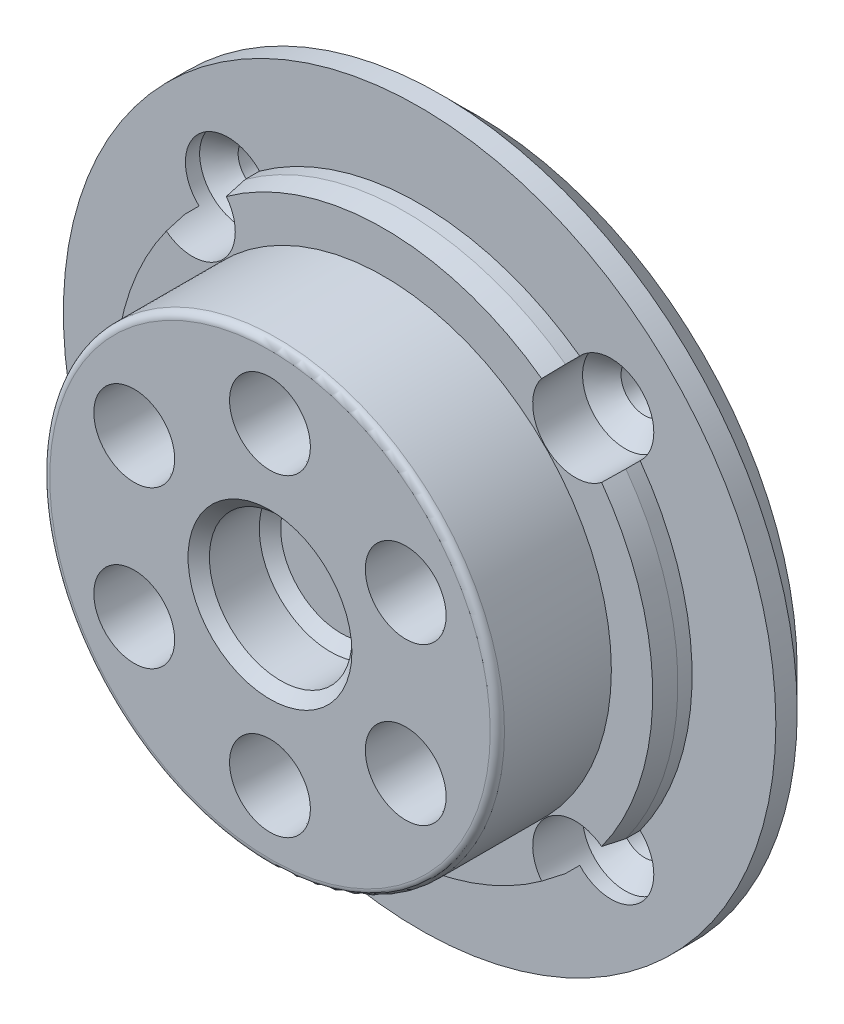
SolidWorks part; units mm, degrees
ref_plane "Front Plane" through (0, 0, 0) normal (0, 0, 1) x (1, 0, 0)
ref_plane "Top Plane" through (0, 0, 0) normal (0, 1, 0) x (1, 0, 0)
ref_plane "Right Plane" through (0, 0, 0) normal (1, 0, 0) x (0, 0, -1)
sketch "Sketch1" plane through (0, 0, 0) normal (0, 0, 1) x (1, 0, 0)
  circle A0 centre (0, 0) radius 25
  dimension "D1" = 50
extrude "Boss-Extrude1" add sketch "Sketch1" along normal blind 4
sketch "Sketch2" plane through (0, 0, 4) normal (0, 0, 1) x (1, 0, 0)
  circle A0 centre (0, 0) radius 19.125
  dimension "D1" = 38.25
extrude "Boss-Extrude2" add sketch "Sketch2" along normal blind 2.5
sketch "Sketch3" plane through (0, 0, 6.5) normal (0, 0, 1) x (1, 0, 0)
  circle A0 centre (0, 0) radius 15.9575
  dimension "D1" = 31.915
extrude "Boss-Extrude3" add sketch "Sketch3" along normal blind 8
sketch "Sketch4" plane through (0, 0, 0) normal (0, 0, -1) x (-1, 0, 0)
  circle A0 centre (0, 16.9333) radius 2.5
  circle A1 centre (16.9333, 0) radius 2.5
  circle A2 centre (0, -16.9333) radius 2.5
  circle A3 centre (-16.9333, 0) radius 2.5
  point P12 (0, 0)
  dimension "D1" = 16.9333
  dimension "D2" = 5
  dimension "D3" = 4
extrude "Cut-Extrude1" cut sketch "Sketch4" against normal blind 3
sketch "Sketch7" plane through (0, 0, 14.5) normal (0, 0, 1) x (1, 0, 0)
  circle A0 centre (0, 11) radius 2.5
  circle A1 centre (9.5263, 5.5) radius 2.5
  circle A2 centre (9.5263, -5.5) radius 2.5
  circle A3 centre (0, -11) radius 2.5
  circle A4 centre (-9.5263, -5.5) radius 2.5
  circle A5 centre (-9.5263, 5.5) radius 2.5
  point P15 (0, 0)
  dimension "D1" = 11
  dimension "D2" = 5
  dimension "D3" = 6
extrude "Cut-Extrude3" cut sketch "Sketch7" against normal blind 11
sketch "Sketch8" plane through (0, 0, 0) normal (0, 0, -1) x (-1, 0, 0)
  circle A0 centre (0, 0) radius 5
  dimension "D1" = 10
extrude "Cut-Extrude4" cut sketch "Sketch8" against normal blind 4
chamfer "Chamfer1" distance 2.5 angle 45 1 edges at (25, 0, 0)
fillet "Fillet1" radius 0.5 1 edges at (15.9575, 0, 14.5)
sketch "Sketch11" plane through (0, 0, 4) normal (0, 0, 1) x (1, 0, 0)
  line L0 (0, 0) -> (-22.4299, 22.4299) construction
  circle A0 centre (-13.435, 13.435) radius 1.65
  circle A1 centre (13.435, 13.435) radius 1.65
  circle A2 centre (13.435, -13.435) radius 1.65
  circle A3 centre (-13.435, -13.435) radius 1.65
  point P14 (0, 0)
  dimension "D1" = 3.3
  dimension "D2" = 19
  dimension "D3" = 4
extrude "Cut-Extrude7" cut sketch "Sketch11" against normal through all both and the other way through all
sketch "Sketch12" plane through (0, 0, 6.5) normal (0, 0, 1) x (1, 0, 0)
  circle A0 centre (-13.435, 13.435) radius 3
  circle A1 centre (13.435, 13.435) radius 3
  circle A2 centre (13.435, -13.435) radius 3
  circle A3 centre (-13.435, -13.435) radius 3
  point P12 (0, 0)
  dimension "D1" = 6
  dimension "D2" = 4
extrude "Cut-Extrude8" cut sketch "Sketch12" against normal blind 5
sketch "Sketch13" plane through (0, 0, 0) normal (0, 0, -1) x (-1, 0, 0)
  circle A0 centre (-10, 0) radius 1.25
  circle A1 centre (-5, 8.6603) radius 1.25
  circle A2 centre (5, 8.6603) radius 1.25
  circle A3 centre (10, 0) radius 1.25
  circle A4 centre (5, -8.6603) radius 1.25
  circle A5 centre (-5, -8.6603) radius 1.25
  point P15 (0, 0)
  dimension "D1" = 2.5
  dimension "D2" = 10
  dimension "D3" = 6
extrude "Cut-Extrude9" [suppressed] cut sketch "Sketch13" against normal blind 12
sketch "Sketch14" [suppressed] plane through (0, 0, 0) normal (0, 0, -1) x (-1, 0, 0)
  circle A0 centre (-10, 0) radius 3
  circle A1 centre (-5, 8.6603) radius 3
  circle A2 centre (5, 8.6603) radius 3
  circle A3 centre (10, 0) radius 3
  circle A4 centre (5, -8.6603) radius 3
  circle A5 centre (-5, -8.6603) radius 3
  point P16 (0, 0)
  dimension "D1" = 6
  dimension "D2" = 6
extrude "Cut-Extrude10" [suppressed] cut sketch "Sketch14" against normal blind 3
sketch "Sketch15" plane through (0, 0, 14.5) normal (0, 0, 1) x (1, 0, 0)
  circle A0 centre (0, 0) radius 5
  dimension "D1" = 10
extrude "Cut-Extrude11" cut sketch "Sketch15" against normal blind 5
chamfer "Chamfer2" distance 1.5 angle 45 4 edges at (16.435, -13.435, 1.5) (-10.435, -13.435, 1.5) (16.435, 13.435, 1.5) (-10.435, 13.435, 1.5)
fillet "Fillet2" radius 2 1 edges at (-5, 0, 4)
chamfer "Chamfer3" distance 1.5 angle 10 4 edges at (0, -19.125, 6.5) (-19.125, 0, 6.5) (19.125, 0, 6.5) (0, 19.125, 6.5) first distance on face at (0, -17.3005, 5.25) first distance on face at (-17.3005, 0, 5.25) first distance on face at (17.3005, 0, 5.25) first distance on face at (0, 17.3005, 5.25)
chamfer "Chamfer4" distance 0.75 angle 45 1 edges at (5, 0, 9.5)
chamfer "Chamfer5" distance 0.75 angle 45 1 edges at (5, 0, 14.5)
sketch "Sketch16" plane through (0, 0, 3.5) normal (0, 0, 1) x (1, 0, 0)
  circle A0 centre (-9.5263, -5.5) radius 0.75
  circle A1 centre (-9.5263, 5.5) radius 0.75
  circle A2 centre (0, 11) radius 0.75
  circle A3 centre (9.5263, 5.5) radius 0.75
  circle A4 centre (9.5263, -5.5) radius 0.75
  circle A5 centre (0, -11) radius 0.75
  point P16 (0, 0)
  dimension "D1" = 1.5
  dimension "D2" = 6
extrude "Cut-Extrude12" cut sketch "Sketch16" against normal through all
chamfer "Chamfer6" distance 0.4 angle 45 4 edges at (-2.5, 16.9333, 0) (-19.4333, 0, 0) (-2.5, -16.9333, 0) (14.4333, 0, 0)
draft "Draft1" type of draft neutral plane draft angle 1.75 faces to draft 6 face at (12.0263, 5.5, 3.5) face at (2.5, 11, 3.5) face at (-7.0263, 5.5, 3.5) face at (-7.0263, -5.5, 3.5) face at (2.5, -11, 3.5) face at (12.0263, -5.5, 3.5) neutral plane through (9.5263, -5.5, 3.5) neutral plane normal (0, 0, 1) parameters "D1"=1.75
draft "Draft2" type of draft neutral plane draft angle 1 faces to draft 4 face at (2.5, -16.9333, 0.4) face at (-14.4333, 0, 0.4) face at (19.4333, 0, 0.4) face at (2.5, 16.9333, 0.4) neutral plane through (0, 16.9333, 3) neutral plane normal (0, 0, -1) parameters "D1"=1
